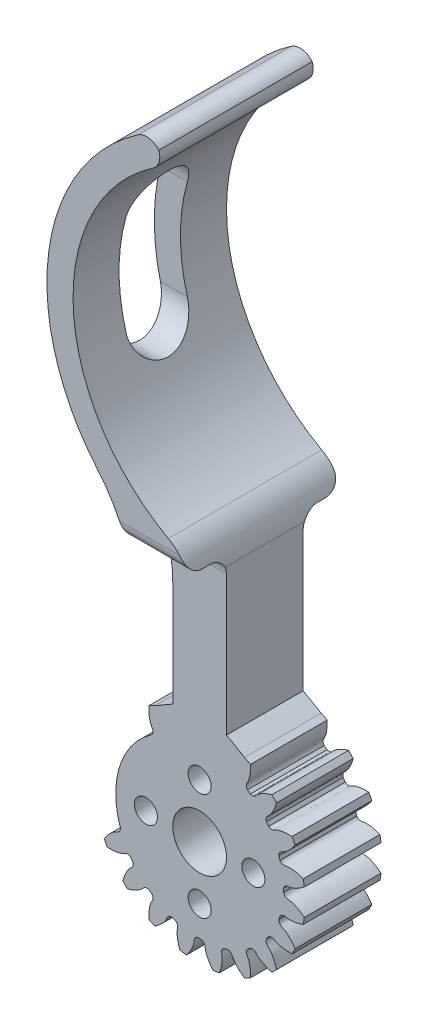
SolidWorks part; units mm, degrees
material "聚脂树脂"
ref_plane "前视基准面" through (0, 0, 0) normal (0, 0, 1) x (1, 0, 0)
ref_plane "上视基准面" through (0, 0, 0) normal (0, 1, 0) x (1, 0, 0)
ref_plane "右视基准面" through (0, 0, 0) normal (1, 0, 0) x (0, 0, -1)
other "Configuration Table"
sketch "草图1" plane through (0, 0, 0) normal (0, 0, 1) x (1, 0, 0)
  circle A0 centre (0, 0) radius 13.75
extrude "凸台-拉伸1" add sketch "草图1" along normal blind 10
ref_axis "基准轴1" through (0, 0, -1.5) along (0, 0, 1)
sketch "草图2" plane through (0, 0, 0) normal (0, 0, 1) x (1, 0, 0)
  line L0 (0, 0) -> (0, 13.75) construction
  circle A0 centre (0, 0) radius 13.75 construction
  arc A1 (0.2416, 10.9348) -> (-0.2416, 10.9348) centre (0, 0) ccw
  arc A2 (3.9764, 15.6228) -> (-3.9764, 15.6228) centre (0, 0) ccw
  spline S0 degree 3 poles (0.2416, 10.9348) (0.764, 11.1168) (0.6964, 11.4839) (0.7661, 11.8375) (0.7736, 11.8719) (0.7829, 11.9108) (0.7941, 11.954) (0.8075, 12.0015) (0.8231, 12.0532) (0.8413, 12.1091) (0.8621, 12.169) (0.8857, 12.2329) (0.9123, 12.3007) (0.9421, 12.3723) (0.9752, 12.4476) (1.0117, 12.5264) (1.0519, 12.6088) (1.0959, 12.6945) (1.1438, 12.7834) (1.1957, 12.8755) (1.2519, 12.9705) (1.3125, 13.0684) (1.3775, 13.1691) (1.4472, 13.2723) (1.5216, 13.3779) (1.601, 13.4858) (1.6853, 13.5958) (1.7747, 13.7078) (1.8694, 13.8216) (1.9693, 13.937) (2.0748, 14.0539) (2.1857, 14.1721) (2.3023, 14.2914) (2.4246, 14.4116) (2.5527, 14.5326) (2.6866, 14.6542) (2.8265, 14.7761) (2.9725, 14.8983) (3.1245, 15.0204) (3.2826, 15.1424) (3.4469, 15.2639) (3.6768, 15.427) (3.8549, 15.5454) (3.9764, 15.6228) knots 0 0 0 0 0.165916 0.170906 0.176664 0.183189 0.190482 0.198542 0.207371 0.216967 0.22733 0.238462 0.250361 0.263027 0.276462 0.290664 0.305634 0.321371 0.337876 0.355149 0.37319 0.391998 0.411574 0.431917 0.453028 0.474907 0.497554 0.520968 0.54515 0.570099 0.595817 0.622302 0.649554 0.677575 0.706363 0.735918 0.766242 0.797333 0.829191 0.861818 0.895212 0.929373 1 1 1 1
  spline S1 degree 3 poles (-0.2416, 10.9348) (-0.764, 11.1168) (-0.6964, 11.4839) (-0.7661, 11.8375) (-0.7736, 11.8719) (-0.7829, 11.9108) (-0.7941, 11.954) (-0.8075, 12.0015) (-0.8231, 12.0532) (-0.8413, 12.1091) (-0.8621, 12.169) (-0.8857, 12.2329) (-0.9123, 12.3007) (-0.9421, 12.3723) (-0.9752, 12.4476) (-1.0117, 12.5264) (-1.0519, 12.6088) (-1.0959, 12.6945) (-1.1438, 12.7834) (-1.1957, 12.8755) (-1.2519, 12.9705) (-1.3125, 13.0684) (-1.3775, 13.1691) (-1.4472, 13.2723) (-1.5216, 13.3779) (-1.601, 13.4858) (-1.6853, 13.5958) (-1.7747, 13.7078) (-1.8694, 13.8216) (-1.9693, 13.937) (-2.0748, 14.0539) (-2.1857, 14.1721) (-2.3023, 14.2914) (-2.4246, 14.4116) (-2.5527, 14.5326) (-2.6866, 14.6542) (-2.8265, 14.7761) (-2.9725, 14.8983) (-3.1245, 15.0204) (-3.2826, 15.1424) (-3.4469, 15.2639) (-3.6768, 15.427) (-3.8549, 15.5454) (-3.9764, 15.6228) knots 0 0 0 0 0.165916 0.170906 0.176664 0.183189 0.190482 0.198542 0.207371 0.216967 0.22733 0.238462 0.250361 0.263027 0.276462 0.290664 0.305634 0.321371 0.337876 0.355149 0.37319 0.391998 0.411574 0.431917 0.453028 0.474907 0.497554 0.520968 0.54515 0.570099 0.595817 0.622302 0.649554 0.677575 0.706363 0.735918 0.766242 0.797333 0.829191 0.861818 0.895212 0.929373 1 1 1 1
extrude "切除-拉伸1" cut sketch "草图2" along normal through all
pattern_circular "阵列(圆周)1" count 20 every 18 about axis through (0, 0, -1.5) along (0, 0, 1) of "切除-拉伸1"
sketch "草图3" plane through (0, 0, 0) normal (0, 0, 1) x (1, 0, 0)
  circle A0 centre (0, 0) radius 12.5 construction
  dimension "Dn" = 25
sketch "草图6" plane through (0, 0, 0) normal (0, 0, -1) x (-1, 0, 0)
  line L0 (0, 0) -> (0, 65.9124) construction
  line L1 (0, 0) -> (39.45, 0) construction
  line L2 (0, 0) -> (-30.8379, 0) construction
  line L3 (-12.5, 0) -> (-12.5, 56.4778) construction
  line L4 (3.5, 0) -> (3.5, 35.9714)
  line L5 (-3.5, 0) -> (-3.5, 35.9714)
  line L6 (-3.5, 35.9714) -> (-3.5, 73.8085)
  line L7 (-3.5, 73.8085) -> (-12.5, 58.22) construction
  line L8 (-3.5, 73.8085) -> (6.3052, 90.7916) construction
  line L9 (-3.5, 73.8085) -> (1.2022, 81.9529)
  line L10 (-3.5, 0) -> (3.5, 0)
  line L11 (-5.8534, 12.4419) -> (-3.5, 13.8006)
  line L12 (5.8534, 12.4419) -> (3.5, 13.8006)
  circle A0 centre (0, 0) radius 12.5 construction
  circle A1 centre (-12.5, 58.22) radius 24 construction
  circle A2 centre (-12.5, 58.22) radius 27.4044 construction
  arc A3 (1.2022, 81.9529) -> (3.5, 35.9714) centre (-12.5, 58.22) cw
  arc A4 (-0.5, 79.0046) -> (-3.5, 35.9714) centre (-12.5, 58.22) cw
  spline S0 degree 3 poles (2502.66, 1658.782) (-28.7069, -14.6032) (-1.7191, 6.2407) (-4.3931, 11.033) (-4.4189, 11.076) (-4.4589, 11.1387) (-4.5098, 11.2131) (-4.5827, 11.3111) (-4.6712, 11.4208) (-4.7765, 11.541) (-4.8994, 11.6706) (-5.0408, 11.8083) (-5.2016, 11.9528) (-5.3825, 12.1027) (-5.5474, 12.2287) (-5.6899, 12.331) (-28.3078, 27.8963) (-140.1993, -89.1599) (2777.6606, 1130.6237) knots -2.506621 -2.506621 -2.506621 -2.506621 0.165916 0.170906 0.183189 0.190482 0.207371 0.22733 0.250361 0.276462 0.305634 0.337876 0.37319 0.411574 0.453028 0.474907 0.497554 13.91055 13.91055 13.91055 13.91055 only from (-3.6089, 10.325) to (-5.8534, 12.4419) construction
  spline S1 degree 3 poles (-3.5, 10.3269) (-4.1564, 10.2919) (-4.2008, 10.6883) (-4.3931, 11.033) (-4.4189, 11.076) (-4.4589, 11.1387) (-4.5098, 11.2131) (-4.5827, 11.3111) (-4.6712, 11.4208) (-4.7765, 11.541) (-4.8994, 11.6706) (-5.0408, 11.8083) (-5.2016, 11.9528) (-5.3825, 12.1027) (-5.5842, 12.2567) (-5.7442, 12.3691) (-5.8366, 12.4308) (-5.8534, 12.4419) knots -0.010289 -0.010289 -0.010289 -0.010289 0.165916 0.170906 0.183189 0.190482 0.207371 0.22733 0.250361 0.276462 0.305634 0.337876 0.37319 0.411574 0.453028 0.497554 0.507432 0.507432 0.507432 0.507432
  spline S2 degree 3 poles (-2502.66, 1658.782) (28.7069, -14.6032) (1.7191, 6.2407) (4.3931, 11.033) (4.4189, 11.076) (4.4589, 11.1387) (4.5098, 11.2131) (4.5827, 11.3111) (4.6712, 11.4208) (4.7765, 11.541) (4.8994, 11.6706) (5.0408, 11.8083) (5.2016, 11.9528) (5.3825, 12.1027) (5.5474, 12.2287) (5.6899, 12.331) (28.3078, 27.8963) (140.1993, -89.1599) (-2777.6606, 1130.6237) knots -2.014052 -2.014052 -2.014052 -2.014052 0.658484 0.663474 0.675757 0.68305 0.699939 0.719899 0.742929 0.76903 0.798202 0.830445 0.865758 0.904142 0.945597 0.967475 0.990122 14.403118 14.403118 14.403118 14.403118 only from (3.6089, 10.325) to (5.8534, 12.4419) construction
  spline S3 degree 3 poles (3.5, 10.3269) (4.1564, 10.2919) (4.2008, 10.6883) (4.3931, 11.033) (4.4189, 11.076) (4.4589, 11.1387) (4.5098, 11.2131) (4.5827, 11.3111) (4.6712, 11.4208) (4.7765, 11.541) (4.8994, 11.6706) (5.0408, 11.8083) (5.2016, 11.9528) (5.3825, 12.1027) (5.5842, 12.2567) (5.7442, 12.3691) (5.8366, 12.4308) (5.8534, 12.4419) knots 0.482279 0.482279 0.482279 0.482279 0.658484 0.663474 0.675757 0.68305 0.699939 0.719899 0.742929 0.76903 0.798202 0.830445 0.865758 0.904142 0.945597 0.990122 1 1 1 1
  dimension "D1" = 25
  dimension "D4" = 48
  dimension "D5" = 30
  dimension "D2" = 7
  dimension "D3" = 58.22
  dimension "D6" = 60
  dimension "D7" = 60
extrude "凸台-拉伸2" add sketch "草图6" against normal blind 15 and the other way blind 5 contours A3 L9 L6 L5 L10 L4 | S1 L5 L11 | L4 S3 L12 region at (0, 0.8399, 0) region at (-4.2531, 12.1172, 0) region at (4.2531, 12.1172, 0)
sketch "草图7" plane through (3.5, 0, 0) normal (1, 0, 0) x (0, 0, -1)
  line L0 (0, 0) -> (0, 34)
  line L1 (0, 34) -> (5, 34)
  line L3 (5, 34) -> (5, 0)
  line L4 (5, 0) -> (0, 0) construction
  line L5 (5, 0) -> (5, 10.3269) construction
  line L6 (5, 0) -> (0, 0)
  line L7 (-5, 2.5777) -> (-5, 27.3083) construction
  line L8 (-10, 2.5777) -> (0, 2.5777) construction
  line L9 (-15, 34) -> (-15, 0)
  line L10 (-10, 34) -> (-15, 34)
  line L11 (-10, 0) -> (-10, 34)
  line L12 (-15, 0) -> (-10, 0)
  dimension "D1" = 34
extrude "切除-拉伸3" cut sketch "草图7" against normal blind 32 and the other way blind 10
ref_plane "基准面1" through (12.5, 0, 0) normal (1, 0, 0) x (0, 0, -1)
sketch "草图10" plane through (12.5, 0, 0) normal (1, 0, 0) x (0, 0, -1)
  line L1 (-5, 0.2416) -> (-5, 79.5715) construction
  line L2 (-5, 82.4616) -> (-5, 34.4616)
  line L3 (-10, 0.2416) -> (0, 0.2416) construction
  arc A1 (-5, 82.4616) -> (-5, 34.4616) centre (-5, 58.4616) cw
  dimension "D1" = 24
  dimension "D2" = 58.22
sketch "草图12" plane through (0, 0, -5) normal (0, 0, -1) x (-1, 0, 0)
  line L0 (0, 0) -> (0, 91.6895) construction
  line L1 (-12.5, -0.9508) -> (-12.5, 90.4677) construction
  line L2 (1.15, 81.8625) -> (1.2022, 81.9529)
  line L4 (-0.5, 79.0046) -> (1.2022, 81.9529) construction
  line L5 (3.5, 35.9714) -> (3.5, 36.1001)
  circle A0 centre (-12.5, 58.22) radius 27.4044
  circle A1 centre (-12.5, 58.22) radius 27.3
  arc A3 (3.5, 35.9714) -> (1.2022, 81.9529) centre (-12.5, 58.22) ccw construction
  dimension "D3" = 54.6
  dimension "D1" = 12.5
  dimension "D2" = 58.22
fillet "圆角2" radius 2 4 edges at (0, 34, 10) (0, 34, 15) (0, 34, 0) (0, 34, -5)
sketch "草图4" plane through (0, 0, 10) normal (0, 0, 1) x (1, 0, 0)
  line L0 (0, 0) -> (0, 14.4175) construction
  line L1 (0, 0) -> (19.7904, 0) construction
  circle A0 centre (0, 0) radius 9
  circle A1 centre (0, 0) radius 3.5
  circle A2 centre (0, 7) radius 1.5
  circle A3 centre (7, 0) radius 1.5
  circle A4 centre (0, -7) radius 1.5
  circle A5 centre (-7, 0) radius 1.5
  dimension "D1" = 18
  dimension "D2" = 7
  dimension "D3" = 3
  dimension "D4" = 3
  dimension "D5" = 7
  dimension "D6" = 7
extrude "切除-拉伸2" cut sketch "草图4" against normal blind 20 contours A1 | A5 | A2 | A3 | A4
sketch "草图13" plane through (0, 0, 0) normal (0, 0, -1) x (-1, 0, 0)
  circle A0 centre (0, 0) radius 10
  circle A1 centre (0, -7) radius 1.5 construction
  circle A2 centre (7, 0) radius 1.5 construction
  circle A3 centre (0, 7) radius 1.5 construction
  circle A5 centre (-7, 0) radius 1.5 construction
  circle A6 centre (0, -7) radius 1.5
  circle A7 centre (7, 0) radius 1.5
  circle A8 centre (0, 7) radius 1.5
  circle A10 centre (-7, 0) radius 1.5
  circle A11 centre (0, 0) radius 1.5
  dimension "D1" = 20
  dimension "D2" = 3
ref_plane "基准面2" through (0, 0, 9) normal (0, 0, 1) x (1, 0, 0)
sketch "草图16" plane through (0, 0, 9) normal (0, 0, 1) x (1, 0, 0)
  circle A0 centre (0, 0) radius 12.5 construction
  dimension "D1" = 25
sketch "草图17" plane through (0, 0, 10) normal (0, 0, 1) x (1, 0, 0)
  line L0 (0, 0) -> (-6.6228, 8.7044)
  line L1 (-6.6228, 8.7044) -> (-11.857, 15.5837)
  line L2 (0, 0) -> (-10.325, -3.6089)
  line L3 (-10.325, -3.6089) -> (-17.9409, -6.2709)
  circle A0 centre (0, 0) radius 10.9375
  arc A1 (-6.2318, 8.9885) -> (-6.6228, 8.7044) centre (0, 0) ccw construction
  circle A2 centre (0, 0) radius 17.5
  dimension "D1" = 35
extrude "切除-拉伸5" cut sketch "草图17" against normal blind 10 contours L1 A2 L3 A0 region at (-12.9643, 3.8979, 10)
sketch "草图18" plane through (0, 0, 0) normal (1, 0, 0) x (0, 0, -1)
  line L0 (-5, 0.2416) -> (-5, 83.1767) construction
  line L1 (-10, 0.2416) -> (0, 0.2416) construction
  circle A0 centre (-5, 58.22) radius 4
  dimension "D1" = 8
  dimension "D2" = 58.22
fillet "圆角3" radius 20 1 edges at (-3.5, 35.9714, 5)
fillet "圆角4" radius 5 1 edges at (3.5, 35.9714, 5)
fillet "圆角5" radius 2 2 edges at (-1.2022, 81.9529, 5) (0.5, 79.0046, 5)
sketch "草图19" plane through (12.5, 0, 0) normal (1, 0, 0) x (0, 0, -1)
  line L0 (-5, 0.2416) -> (-5, 85.5937) construction
  line L1 (-10, 0.2416) -> (0, 0.2416) construction
  line L2 (-5, 64.72) -> (-5, 51.72) construction
  line L3 (-1, 64.72) -> (-1, 51.72)
  line L4 (-9, 64.72) -> (-9, 51.72)
  arc A0 (-1, 64.72) -> (-9, 64.72) centre (-5, 64.72) ccw
  arc A1 (-9, 51.72) -> (-1, 51.72) centre (-5, 51.72) ccw
  point P6 (-5, 58.22)
  dimension "D3" = 4
  dimension "D1" = 58.22
  dimension "D2" = 13
extrude "切除-拉伸6" cut sketch "草图19" against normal blind 55
